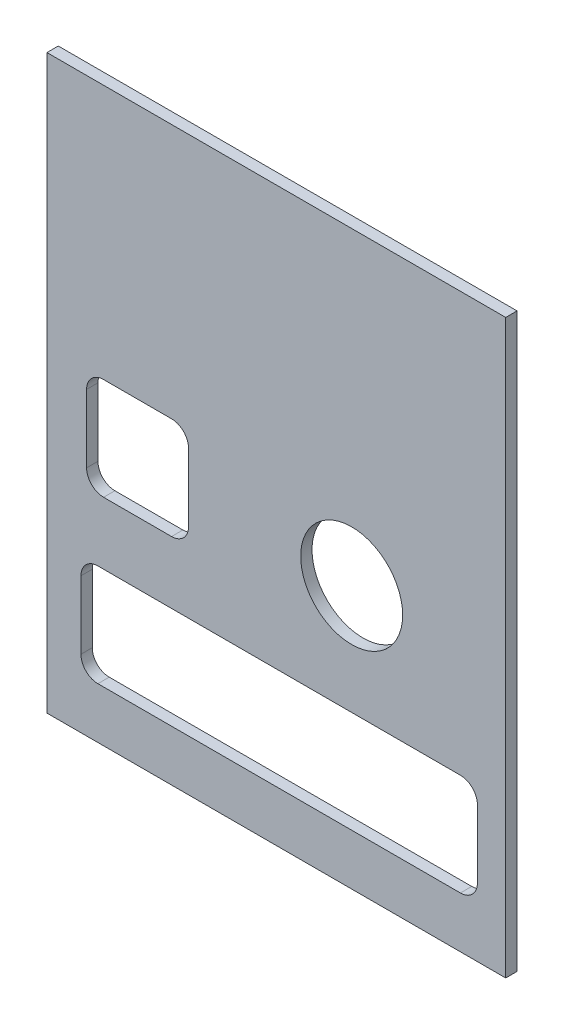
SolidWorks part; units mm, degrees
ref_plane "Front Plane" through (0, 0, 0) normal (0, 0, 1) x (1, 0, 0)
ref_plane "Top Plane" through (0, 0, 0) normal (0, 1, 0) x (1, 0, 0)
ref_plane "Right Plane" through (0, 0, 0) normal (1, 0, 0) x (0, 0, -1)
sketch "Sketch1" plane through (0, 0, 0) normal (0, 0, 1) x (1, 0, 0)
  line L1 (-48.8946, 55.0473) -> (32.1054, 55.0473)
  line L2 (-48.8946, 55.0473) -> (-48.8946, -45.9527)
  line L3 (-48.8946, -45.9527) -> (32.1054, -45.9527)
  line L4 (32.1054, 55.0473) -> (32.1054, -45.9527)
extrude "Boss-Extrude1" add sketch "Sketch1" along normal blind 2
sketch "Sketch2" plane through (0, 0, 2) normal (0, 0, 1) x (1, 0, 0)
  line L3 (-39.8946, -18.9527) -> (24.1054, -18.9527)
  line L4 (-42.8946, -21.9527) -> (-42.8946, -33.9527)
  line L5 (-39.8946, -36.9527) -> (24.1054, -36.9527)
  line L6 (27.1054, -21.9527) -> (27.1054, -33.9527)
  line L7 (-48.8946, 55.0473) -> (-48.8946, -45.9527) construction
  line L8 (-48.8946, -45.9527) -> (32.1054, -45.9527) construction
  line L15 (-38.8946, 10.0473) -> (-26.8946, 10.0473)
  line L16 (-41.8946, 7.0473) -> (-41.8946, -4.9527)
  line L17 (-38.8946, -7.9527) -> (-26.8946, -7.9527)
  line L18 (-23.8946, 7.0473) -> (-23.8946, -4.9527)
  arc A2 (24.1054, -18.9527) -> (27.1054, -21.9527) centre (24.1054, -21.9527) cw
  arc A3 (-42.8946, -33.9527) -> (-39.8946, -36.9527) centre (-39.8946, -33.9527) ccw
  arc A4 (24.1054, -36.9527) -> (27.1054, -33.9527) centre (24.1054, -33.9527) ccw
  arc A5 (-39.8946, -18.9527) -> (-42.8946, -21.9527) centre (-39.8946, -21.9527) ccw
  arc A6 (-41.8946, -4.9527) -> (-38.8946, -7.9527) centre (-38.8946, -4.9527) ccw
  arc A7 (-26.8946, -7.9527) -> (-23.8946, -4.9527) centre (-26.8946, -4.9527) ccw
  arc A8 (-26.8946, 10.0473) -> (-23.8946, 7.0473) centre (-26.8946, 7.0473) cw
  arc A9 (-38.8946, 10.0473) -> (-41.8946, 7.0473) centre (-38.8946, 7.0473) ccw
  circle A11 centre (4.9054, 0.4326) radius 9
  point P11 (27.1054, -18.9527)
  point P14 (-42.8946, -36.9527)
  point P18 (27.1054, -36.9527)
  point P27 (-23.8946, -7.9527)
  point P30 (-23.8946, 10.0473)
  point P33 (-41.8946, 10.0473)
  dimension "D1" = 70
  dimension "D5" = 3
  dimension "D6" = 3
  dimension "D11" = 3
  dimension "D12" = 18
  dimension "D2" = 6
  dimension "D3" = 18
  dimension "D4" = 9
  dimension "D7" = 18
  dimension "D8" = 18
  dimension "D9" = 7
  dimension "D10" = 11
extrude "Cut-Extrude2" cut sketch "Sketch2" against normal blind 2
